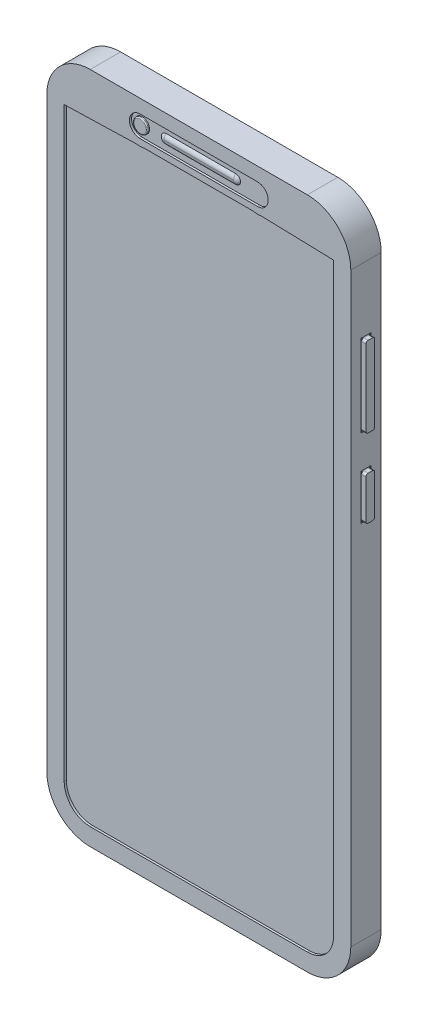
SolidWorks part; units mm, degrees
ref_plane "Front Plane" through (0, 0, 0) normal (0, 0, 1) x (1, 0, 0)
ref_plane "Top Plane" through (0, 0, 0) normal (0, 1, 0) x (1, 0, 0)
ref_plane "Right Plane" through (0, 0, 0) normal (1, 0, 0) x (0, 0, -1)
sketch "Sketch1" plane through (0, 0, 0) normal (0, 0, 1) x (1, 0, 0)
  line L1 (-35, -77.5) -> (35, -77.5)
  line L2 (-35, -77.5) -> (-35, 77.5)
  line L3 (-35, 77.5) -> (35, 77.5)
  line L4 (35, -77.5) -> (35, 77.5)
  line L5 (-35, -77.5) -> (35, 77.5) construction
  line L6 (-35, 77.5) -> (35, -77.5) construction
  point P0 (0, 0)
  dimension "D1" = 155
  dimension "D2" = 70
extrude "Boss-Extrude1" add sketch "Sketch1" along normal blind 7
fillet "Fillet1" radius 10 4 edges at (35, -77.5, 3.5) (-35, -77.5, 3.5) (-35, 77.5, 3.5) (35, 77.5, 3.5)
sketch "Sketch3" plane through (35, 0, 0) normal (1, 0, 0) x (0, 0, -1)
  line L0 (-3.5, 67.5) -> (-3.5, -67.5) construction
  line L1 (-4.5, 52.5) -> (-2.5, 52.5)
  line L2 (-4.5, 52.5) -> (-4.5, 34)
  line L3 (-4.5, 34) -> (-2.5, 34)
  line L4 (-2.5, 52.5) -> (-2.5, 34)
  line L5 (-4.5, 52.5) -> (-2.5, 34) construction
  line L6 (-4.5, 34) -> (-2.5, 52.5) construction
  line L7 (0, 67.5) -> (-7, 67.5) construction
  line L8 (-7, -67.5) -> (0, -67.5) construction
  line L9 (-7, 77.5) -> (0, 77.5) construction
  line L10 (-4.7, 33.8) -> (-2.3, 33.8)
  line L11 (-2.3, 52.7) -> (-2.3, 33.8)
  line L12 (-4.7, 52.7) -> (-2.3, 52.7)
  line L13 (-4.7, 52.7) -> (-4.7, 33.8)
  point P4 (-3.5, 43.25)
  dimension "D1" = 18.5
  dimension "D2" = 2
  dimension "D3" = 25
  dimension "D4" = 0.2
extrude "Cut-Extrude1" cut sketch "Sketch3" against normal blind 2
extrude "Boss-Extrude2" add sketch "Sketch3<2>" along normal blind 1 separate body contours L4 L1 L2 L3 region at (35, 43.25, 3.5)
sketch "Sketch3<2>" plane through (35, 0, 0) normal (1, 0, 0) x (0, 0, -1) same geometry as "Sketch3"
fillet "Fillet2" radius 0.5 4 edges at (35.5, 34, 2.5) (35.5, 34, 4.5) (35.5, 52.5, 2.5) (35.5, 52.5, 4.5)
sketch "Sketch4" plane through (35, 0, 0) normal (1, 0, 0) x (0, 0, -1)
  line L0 (-3.5, 67.5) -> (-3.5, -67.5) construction
  line L1 (0, 67.5) -> (-7, 67.5) construction
  line L2 (-7, -67.5) -> (0, -67.5) construction
  line L3 (-2.3, 15.8) -> (-2.3, 26.2)
  line L4 (-4.5, 16) -> (-2.5, 16)
  line L5 (-4.5, 16) -> (-4.5, 26)
  line L6 (-4.5, 26) -> (-2.5, 26)
  line L7 (-2.5, 16) -> (-2.5, 26)
  line L8 (-4.5, 16) -> (-2.5, 26) construction
  line L9 (-4.5, 26) -> (-2.5, 16) construction
  line L10 (-4.7, 26.2) -> (-2.3, 26.2)
  line L11 (-4.7, 15.8) -> (-4.7, 26.2)
  line L12 (-4.7, 15.8) -> (-2.3, 15.8)
  point P6 (-3.5, 21)
  dimension "D1" = 2
  dimension "D2" = 10
  dimension "D3" = 8
  dimension "D4" = 0.2
extrude "Cut-Extrude2" cut sketch "Sketch4" against normal blind 1
extrude "Boss-Extrude3" add sketch "Sketch4<2>" along normal blind 1 separate body contours L4 L7 L6 L5 region at (35, 21, 3.5)
sketch "Sketch4<2>" plane through (35, 0, 0) normal (1, 0, 0) x (0, 0, -1) same geometry as "Sketch4"
fillet "Fillet3" radius 0.5 4 edges at (35.5, 26, 4.5) (35.5, 26, 2.5) (35.5, 16, 2.5) (35.5, 16, 4.5)
sketch "Sketch6" plane through (0, -77.5, 0) normal (0, -1, 0) x (1, 0, 0)
  line L0 (-35, 3.5) -> (35, 3.5) construction
  line L1 (-35, 0) -> (-35, 7) construction
  line L2 (35, 7) -> (35, 0) construction
  line L3 (25, 0) -> (25, 7) construction
  line L4 (-25, 7) -> (-25, 0) construction
  line L5 (-3.8, 3.5) -> (3.8, 3.5) construction
  line L6 (-3.8, 5.2) -> (3.8, 5.2)
  line L7 (-3.8, 1.8) -> (3.8, 1.8)
  circle A0 centre (-25, 3.5) radius 2
  arc A1 (-3.8, 5.2) -> (-3.8, 1.8) centre (-3.8, 3.5) ccw
  arc A2 (3.8, 1.8) -> (3.8, 5.2) centre (3.8, 3.5) ccw
  circle A3 centre (22, 3.5) radius 1
  circle A4 centre (19, 3.5) radius 1
  circle A5 centre (16, 3.5) radius 1
  circle A6 centre (13, 3.5) radius 1
  circle A7 centre (25, 3.5) radius 1
  point P8 (0, 3.5)
  point P17 (5.5, 3.5)
  point P18 (-5.5, 3.5)
  dimension "D1" = 4
  dimension "D2" = 1.7
  dimension "D4" = 2
  dimension "D3" = 11
  dimension "D5" = 3
  dimension "D6" = 3
  dimension "D7" = 3
  dimension "D8" = 3
extrude "Cut-Extrude3" cut sketch "Sketch6" against normal blind 11
sketch "Sketch7" plane through (0, -66.5, 0) normal (0, -1, 0) x (1, 0, 0)
  line L2 (-3.8, 2.3) -> (3.8, 2.3)
  line L3 (3.8, 4.7) -> (-3.8, 4.7)
  line L4 (-3.8, 2.8) -> (3.8, 2.8)
  line L5 (3.8, 4.2) -> (-3.8, 4.2)
  line L6 (-3.8, 2.8) -> (3.8, 2.8)
  line L7 (3.8, 4.2) -> (-3.8, 4.2)
  arc A2 (-3.8, 4.7) -> (-3.8, 2.3) centre (-3.8, 3.5) ccw
  arc A3 (3.8, 2.3) -> (3.8, 4.7) centre (3.8, 3.5) ccw
  arc A4 (-3.8, 4.2) -> (-3.8, 2.8) centre (-3.8, 3.5) ccw
  arc A5 (3.8, 2.8) -> (3.8, 4.2) centre (3.8, 3.5) ccw
  arc A6 (-3.8, 4.2) -> (-3.8, 2.8) centre (-3.8, 3.5) ccw
  arc A7 (3.8, 2.8) -> (3.8, 4.2) centre (3.8, 3.5) ccw
  dimension "D1" = 1
  dimension "D2" = 0.5
extrude "Boss-Extrude4" add sketch "Sketch7" along normal blind 10
sketch "Sketch8" plane through (0, 0, 7) normal (0, 0, 1) x (1, 0, 0)
  line L0 (-13.5211, 71.9054) -> (13.5211, 71.9054) construction
  line L1 (-13.5211, 74.361) -> (13.5211, 74.361)
  line L2 (-13.5211, 69.4498) -> (13.5211, 69.4498)
  line L3 (-8.0357, 71.9054) -> (8.0357, 71.9054) construction
  line L4 (-8.0357, 72.9783) -> (8.0357, 72.9783)
  line L6 (-12.5802, 68.0176) -> (12.5802, 68.0176)
  line L8 (-25, -73.5) -> (25, -73.5)
  line L9 (31, -67.5) -> (31, 67.5)
  line L10 (25, 73.5) -> (-25, 73.5)
  line L11 (-31, 67.5) -> (-31, -67.5)
  line L12 (-25, -73.5) -> (25, -73.5)
  line L13 (31, -67.5) -> (31, 67.5)
  line L15 (-31, 67.5) -> (-31, -67.5)
  line L16 (-8.0357, 70.8325) -> (8.0357, 70.8325)
  line L17 (-12.5802, 68.0176) -> (-31, 67.5)
  line L18 (12.5802, 68.0176) -> (31, 67.5)
  arc A0 (-13.5211, 74.361) -> (-13.5211, 69.4498) centre (-13.5211, 71.9054) ccw
  arc A1 (13.5211, 69.4498) -> (13.5211, 74.361) centre (13.5211, 71.9054) ccw
  circle A2 centre (-13.5211, 71.9054) radius 1.6786
  arc A3 (-8.0357, 72.9783) -> (-8.0357, 70.8325) centre (-8.0357, 71.9054) ccw
  arc A4 (-14.2421, 67.9709) -> (-12.5802, 68.0176) centre (-13.5211, 71.9054) ccw
  arc A5 (12.5802, 68.0176) -> (14.2421, 67.9709) centre (13.5211, 71.9054) ccw
  arc A6 (8.0357, 70.8325) -> (8.0357, 72.9783) centre (8.0357, 71.9054) ccw
  arc A8 (25, -73.5) -> (31, -67.5) centre (25, -67.5) ccw
  arc A9 (31, 67.5) -> (25, 73.5) centre (25, 67.5) ccw
  arc A10 (-25, 73.5) -> (-31, 67.5) centre (-25, 67.5) ccw
  arc A11 (-31, -67.5) -> (-25, -73.5) centre (-25, -67.5) ccw
  arc A12 (25, -73.5) -> (31, -67.5) centre (25, -67.5) ccw
  arc A15 (-31, -67.5) -> (-25, -73.5) centre (-25, -67.5) ccw
  point P2 (0, 72.0176)
  point P3 (0, 71.9054)
  point P18 (0, 71.9054)
  dimension "D2" = 4
  dimension "D1" = 4
extrude "Cut-Extrude4" cut sketch "Sketch8" against normal blind 0.5 contours L15 A15 L12 A12 L13 L18 A5 L6 A4 L17 | L2 A1 L1 A0 A6 L16 A3 L4 A2 region at (0.0313, 73.9244, 7) region at (-14.7169, 73.1779, 7) region at (0, -2.6971, 7)
fillet "Fillet4" radius 1.3 2 edges at (0, 72.9783, 7) (0, 70.8325, 7)
fillet "Fillet5" radius 0.25 1 edges at (-11.8425, 71.9054, 7)
